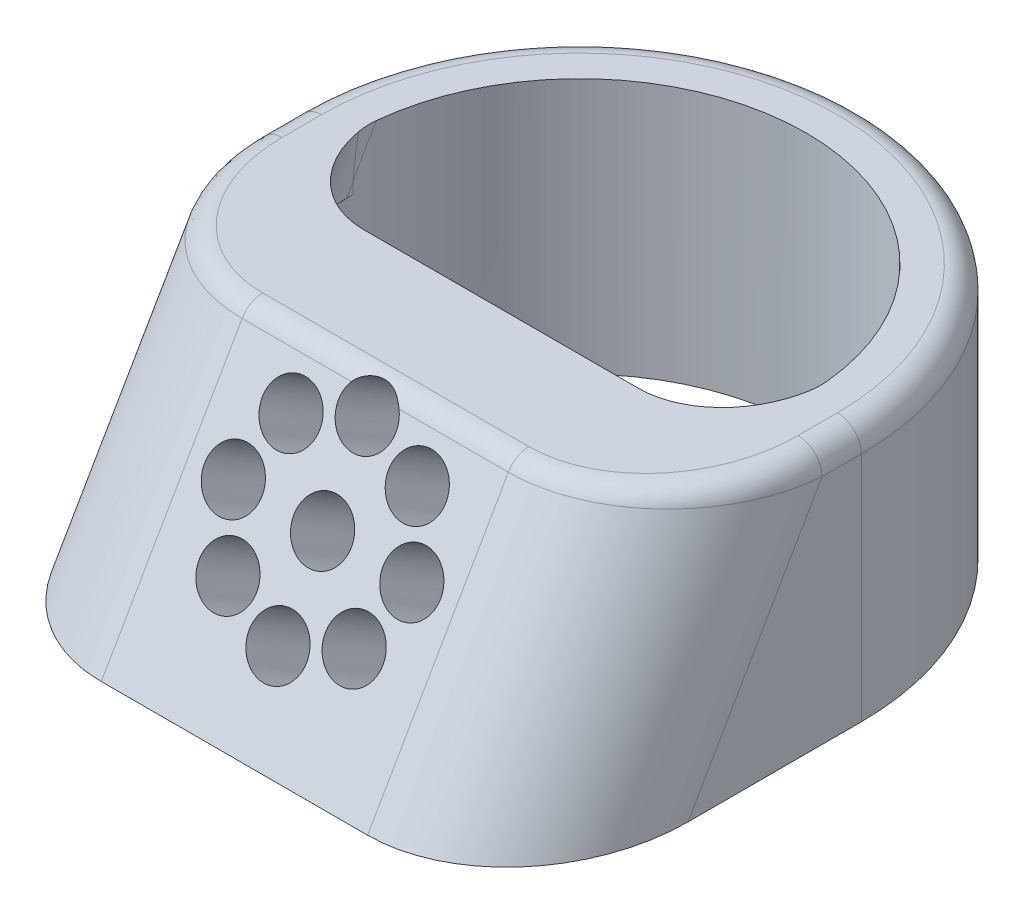
SolidWorks part; units mm, degrees
ref_plane "Front Plane" through (0, 0, 0) normal (0, 0, 1) x (1, 0, 0)
ref_plane "Top Plane" through (0, 0, 0) normal (0, 1, 0) x (1, 0, 0)
ref_plane "Right Plane" through (0, 0, 0) normal (1, 0, 0) x (0, 0, -1)
sketch "Sketch1" plane through (0, 0, 0) normal (0, 1, 0) x (1, 0, 0)
  line L0 (-47.375, 0) -> (-47.375, -22)
  line L2 (47.375, -22) -> (47.375, 0)
  line L3 (-38.1, 0) -> (-38.1, -22)
  line L5 (38.1, -22) -> (38.1, 0)
  line L6 (-47.375, -22) -> (-38.1, -22)
  line L7 (38.1, -22) -> (47.375, -22)
  arc A0 (38.1, 0) -> (-38.1, 0) centre (0, 0) ccw
  arc A1 (47.375, 0) -> (-47.375, 0) centre (0, 0) ccw
  dimension "D1" = 76.2
  dimension "D2" = 47.375
  dimension "D3" = 22
extrude "Boss-Extrude1" add sketch "Sketch1" along normal blind 43
extrude "Boss-Extrude2" add sketch "Sketch1<2>" along normal blind 6.35 contours L5 A0 L3 | L2 A1 L0 A0 L5 L3 region at (0, 0, -46.2007)
sketch "Sketch1<2>" plane through (0, 0, 0) normal (0, 1, 0) x (1, 0, 0) same geometry as "Sketch1"
sketch "Sketch8" plane through (0, 0, 0) normal (1, 0, 0) x (0, 0, -1)
  line L0 (-58, 0) -> (-33.1739, 43)
  line L3 (-38, 0) -> (-58, 0)
  line L4 (-38, 0) -> (-13.1739, 43)
  line L5 (-13.1739, 43) -> (-33.1739, 43)
  line L6 (-22, 43) -> (0, 43) construction
  dimension "D1" = 20
  dimension "D2" = 60
  dimension "D3" = 38
extrude "Boss-Extrude3" add sketch "Sketch8" against normal up to surface and the other way up to surface up to face at (-47.375, 21.5, 11) other way up to face at (47.375, 21.5, 11)
sketch "Sketch9" plane through (0, 16.4545, 28.5) normal (0, -0.5, -0.866) x (1, 0, 0)
  circle A0 centre (0, 6) radius 15
  dimension "D1" = 30
  dimension "D2" = 6
extrude "Cut-Extrude4" [suppressed] cut sketch "Sketch9" against normal through all
sketch "Sketch10" plane through (47.375, 0, 0) normal (1, 0, 0) x (0, 0, -1)
  line L0 (-38, 0) -> (-22, 0)
  line L1 (-22, 0) -> (-22, 27.7128)
  line L2 (-22, 27.7128) -> (-38, 0)
extrude "Boss-Extrude4" add sketch "Sketch10" against normal up to surface (9.275 mm away) up to face at (38.1, 22.7426, 11.4348)
sketch "Sketch11" plane through (-47.375, 0, 0) normal (-1, 0, 0) x (0, 0, 1)
  line L0 (22, 0) -> (38, 0)
  line L1 (38, 0) -> (22, 27.7128)
  line L2 (22, 27.7128) -> (22, 0)
extrude "Boss-Extrude5" add sketch "Sketch11" against normal up to surface (9.275 mm away) up to face at (-38.1, 22.7426, 11.4348)
sketch "Sketch12" plane through (0, 0, 0) normal (0, -1, 0) x (1, 0, 0)
  line L5 (-38.1, 0) -> (-38.1, 38)
  line L6 (-38.1, 38) -> (0, 38.1)
  line L10 (0, 38.1) -> (38.1, 38)
  line L11 (38.1, 38) -> (38.1, 0)
  arc A3 (38.1, 0) -> (-38.1, 0) centre (0, 0) ccw
  line M6 (-38.1, 0) -> (-38.1, 38)
  line M7 (-38.1, 38) -> (38.1, 38)
  line M8 (38.1, 38) -> (38.1, 0)
extrude "Boss-Extrude6" add sketch "Sketch12" against normal blind 34 contours A3 M8 M7 | A3 M7 M6 region at (-29.703, 0, 29.49) region at (29.703, 0, 29.49)
sketch "Sketch13" plane through (0, 25.1147, 43.5) normal (0, 0.5, 0.866) x (1, 0, 0)
  line L1 (-47.375, 20.6521) -> (47.375, 20.6521) construction
  line L2 (0, 15.6521) -> (0, -14.3479) construction
  circle A21 centre (0, 15.6521) radius 4.825
  circle A22 centre (0, -14.3479) radius 4.825
  circle A23 centre (10.6066, 11.2587) radius 4.825
  circle A24 centre (15, 0.6521) radius 4.825
  circle A25 centre (10.6066, -9.9545) radius 4.825
  circle A26 centre (0, -14.3479) radius 4.825
  circle A27 centre (-10.6066, -9.9545) radius 4.825
  circle A28 centre (-15, 0.6521) radius 4.825
  circle A29 centre (-10.6066, 11.2587) radius 4.825
  circle A36 centre (0, 0.6521) radius 4.825
  point P31 (0, 0.6521)
  point P41 (0, 0.6521)
  dimension "D1" = 9.65
  dimension "D2" = 5
  dimension "D3" = 30
  dimension "D4" = 8
extrude "Cut-Extrude6" cut sketch "Sketch13" against normal up to surface (17.3205 mm away) contours A21 | A23 | L2 | A29 | A24 | A25 | A28 | A26 | L2 | A22 | A27 | A36 region at (0, 38.6699, 35.6739) region at (0, 12.6891, 50.6739) region at (10.6066, 34.8651, 37.8706) region at (15, 25.6795, 43.1739) region at (10.6066, 16.4939, 48.4772) region at (-10.6066, 16.4939, 48.4772) region at (-15, 25.6795, 43.1739) region at (-10.6066, 34.8651, 37.8706) up to face at (0, 26.0657, 22.951)
fillet "Fillet8" radius 15 2 edges at (-38.1, 38.5, 15.772) (38.1, 38.5, 15.772)
fillet "Fillet9" radius 25 2 edges at (47.375, 21.5, 45.587) (-47.375, 21.5, 45.587)
sketch "Sketch14" plane through (0, 0, 0) normal (0, -1, 0) x (1, 0, 0)
  circle A0 centre (-42.0864, -4.195) radius 2.125
  circle A1 centre (0, -42.295) radius 2.125
  circle A2 centre (42.0864, -4.195) radius 2.125
  arc A5 (42.0864, -4.195) -> (42.0069, 4.9278) centre (0, 0) cw construction
  arc A6 (-2.7586, 38) -> (2.7586, 38) centre (0, 0) ccw construction
  dimension "D1" = 4.25
  dimension "D4" = 42.295
  dimension "D2" = 38.1
extrude "Cut-Extrude7" cut sketch "Sketch14" against normal blind 8
fillet "Fillet10" radius 10 2 edges
fillet "Fillet11" radius 4 6 edges at (47.375, 43, 2.1532) (40.0527, 43, 24.7188) (0, 43, 33.1739) (-40.0527, 43, 24.7188) (-47.375, 43, 2.1532) (0, 43, -47.375)
